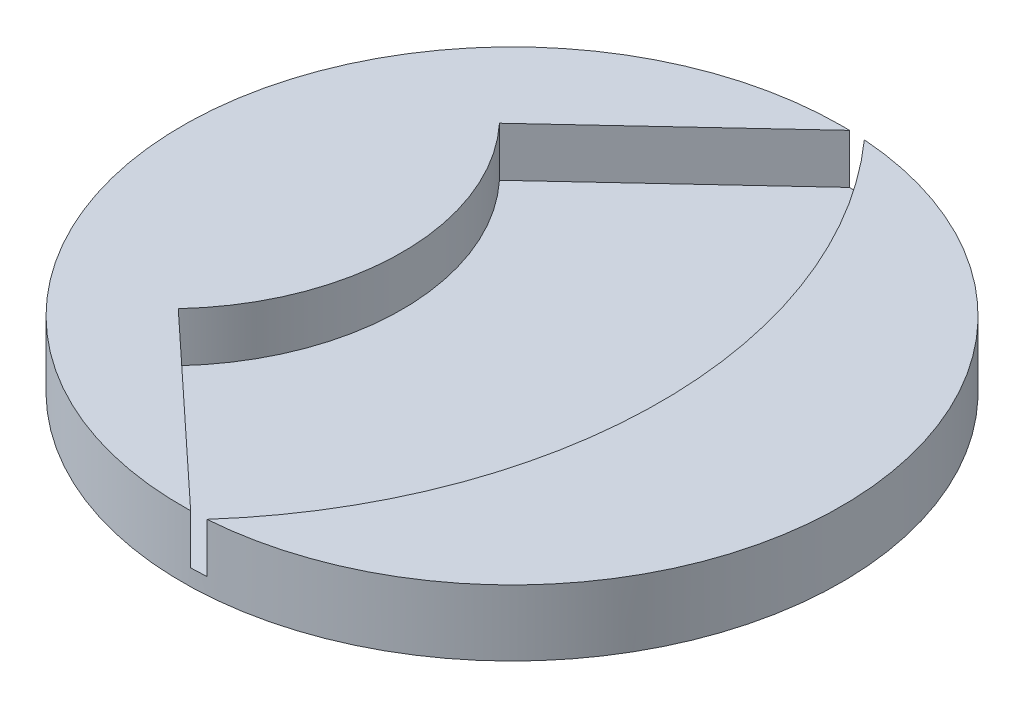
SolidWorks part; units mm, degrees
ref_plane "Front Plane" through (0, 0, 0) normal (0, 0, 1) x (1, 0, 0)
ref_plane "Top Plane" through (0, 0, 0) normal (0, 1, 0) x (1, 0, 0)
ref_plane "Right Plane" through (0, 0, 0) normal (1, 0, 0) x (0, 0, -1)
sketch "Sketch1" plane through (0, 0, 0) normal (0, 0, 1) x (1, 0, 0)
  line L0 (1.15, -2) -> (1.15, 2)
  line L1 (1.15, 2) -> (0, 2)
  line L2 (0, 2) -> (0, 6)
  line L3 (0, 6) -> (20, 6)
  line L4 (20, 6) -> (20, 2)
  line L5 (20, 2) -> (3.15, 2)
  line L6 (3.15, 2) -> (3.15, -2)
  line L7 (3.15, -2) -> (1.15, -2)
  line L8 (0, -3.5392) -> (0, 6.3608) construction
  point P9 (1.15, 0)
  dimension "D1" = 2.3
  dimension "D2" = 2
  dimension "D3" = 4
  dimension "D4" = 4
  dimension "D5" = 40
revolve "Revolve1" add sketch "Sketch1" angle 360 about L8
sketch "Sketch2" plane through (0, 6, 0) normal (0, 1, 0) x (1, 0, 0)
  line L0 (0.9768, 20.4492) -> (-10.5107, 9.7474)
  line L1 (0.9768, -20.4492) -> (-10.5107, -9.7474)
  line L2 (9.0261, 0) -> (-6.6739, 0) construction
  arc A0 (0.9768, 20.4492) -> (0.9768, -20.4492) centre (-20.9739, 0) cw
  arc A1 (-10.5107, 9.7474) -> (-10.5107, -9.7474) centre (-20.9739, 0) cw
  dimension "IR" = 14.3
  dimension "OR" = 30
  dimension "D1" = 20.9739
extrude "Cut-Extrude1" cut sketch "Sketch2" against normal blind 3
equation "\"D1@Sketch2\"=2*(\"OR@Sketch2\"^3-\"IR@Sketch2\"^3)*sin(\"a@Sketch2\")/(3*\"a@Sketch2\"*(\"OR@Sketch2\"^2-\"IR@Sketch2\"^2))"
